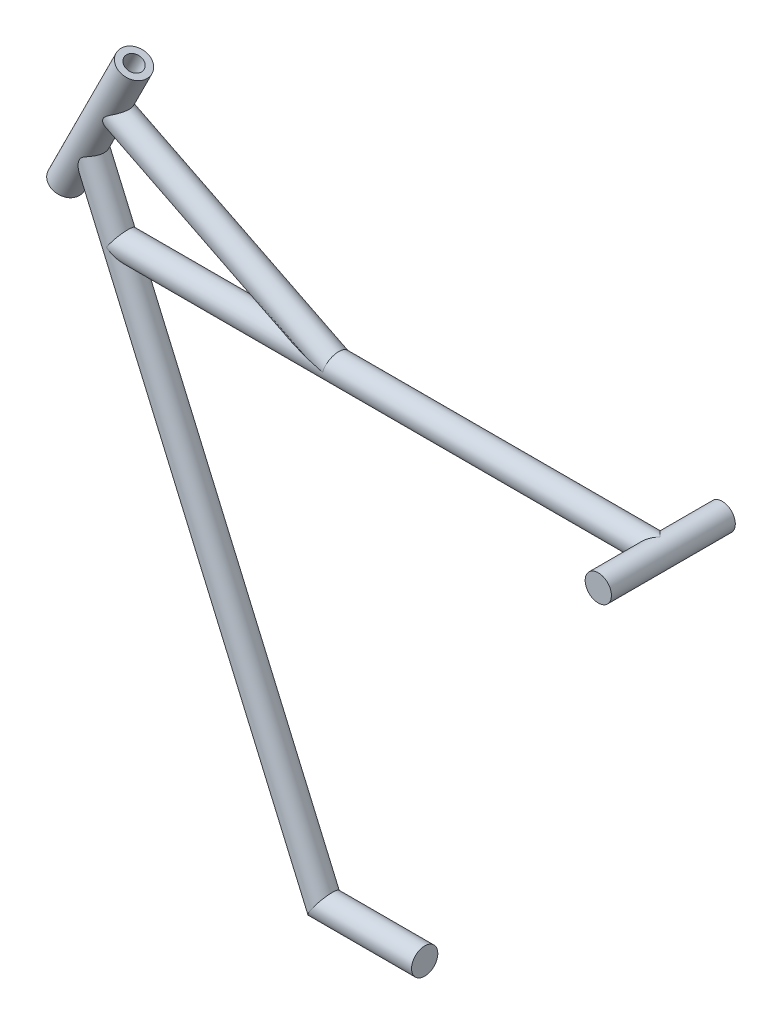
SolidWorks part; units mm, degrees
ref_plane "Спереди" through (0, 0, 0) normal (0, 0, 1) x (1, 0, 0)
ref_plane "Сверху" through (0, 0, 0) normal (0, 1, 0) x (1, 0, 0)
ref_plane "Справа" through (0, 0, 0) normal (1, 0, 0) x (0, 0, -1)
sketch "Эскиз1" plane through (65.3567, 130.5673, 0) normal (0.4476, 0.8942, 0) x (0.8942, -0.4476, 0)
  circle A0 centre (-752.4657, 0) radius 15
  circle A1 centre (-752.4657, 0) radius 8.538
extrude "Бобышка-Вытянуть1" add sketch "Эскиз1" along normal blind 155
sketch "шлях" plane through (0, 0, 0) normal (0, 0, 1) x (1, 0, 0)
  line L1 (-344.3559, -42.0343) -> (-584.115, 511.7691)
  line L5 (-344.3559, -42.0343) -> (-240.4718, -42.0343)
  dimension "D1" = 246.591
ref_plane "Плоскость4" through (-240.4718, 0, 0) normal (1, 0, 0) x (0, 0, -1)
sketch "профіль" plane through (-240.4718, 0, 0) normal (1, 0, 0) x (0, 0, -1)
  circle A0 centre (0, -41.4928) radius 13.45
sweep "По траектории1" add profiles "профіль" path "шлях"
ref_plane "Плоскость5" through (0, -42.0343, 0) normal (0, 1, 0) x (1, 0, 0)
ref_plane "Плоскость7" through (0, 0, 50) normal (0, 0, 1) x (1, 0, 0)
sketch "Эскиз5" plane through (0, 0, 50) normal (0, 0, 1) x (1, 0, 0)
  line L0 (43.8257, 180.5593) -> (-9.8854, 49.4555) construction
  line L1 (100.1108, 212.4383) -> (0.7865, 441.8608)
  line L3 (-4.1424, -42.0343) -> (100.1108, 212.4383)
  line L4 (-335.1669, -28.0428) -> (-568.7095, 511.4016) construction
  line L5 (-4.1424, -42.0343) -> (-279.1424, -42.0343)
  dimension "D1" = 250
  dimension "D2" = 39.9983
  dimension "D3" = 275
  dimension "D4" = 275
ref_plane "Плоскость8" through (0.7865, 441.8608, 50) normal (-0.3973, 0.9177, 0) x (0.9177, 0.3973, 0)
sketch "Эскиз10" plane through (0, 0, 0) normal (0, 0, 1) x (1, 0, 0)
  circle A0 centre (0.7865, 441.8608) radius 13.45
extrude "Бобышка-Вытянуть2" add sketch "Эскиз10" along normal mid plane 126.9 contours A0
sketch "Эскиз11" plane through (0, 0, 0) normal (0, 0, 1) x (1, 0, 0)
  line L0 (0.7865, 441.8608) -> (-553.4001, 441.8608)
  point P5 (-553.4001, 441.8608)
ref_plane "Плоскость10" through (0.7865, 441.8608, 0) normal (-1, 0, 0) x (0, 0, 1)
sketch "Эскиз12" plane through (0.7865, 441.8608, 0) normal (-1, 0, 0) x (0, 0, 1)
  circle A0 centre (0, 0) radius 13.45
  dimension "D1" = 26.9
sweep "По траектории7" add profiles "Эскиз12" path "Эскиз11"
sketch "Эскиз13" plane through (0, 0, 0) normal (0, 0, 1) x (1, 0, 0)
  line L0 (-562.1123, 557.2874) -> (-331.5169, 441.8608)
  line L1 (-498.7232, 455.3108) -> (-498.7232, 428.4108) construction
  line L2 (0.7865, 455.3108) -> (-553.4001, 455.3108) construction
  line L3 (-553.4001, 428.4108) -> (0.7865, 428.4108) construction
  line L4 (-498.7232, 441.8608) -> (-164.3106, 441.8608) construction
  line L5 (-538.1384, 605.9864) -> (-607.5185, 467.3812) construction
  line L6 (-530.5035, 602.1647) -> (-545.7732, 609.8081) construction
  line L7 (-620.9319, 474.0954) -> (-594.1051, 460.667) construction
ref_plane "Плоскость11" through (-331.5169, 441.8608, 0) normal (0.8942, -0.4476, 0) x (0, 0, -1)
sketch "Эскиз14" plane through (-331.5169, 441.8608, 0) normal (0.8942, -0.4476, 0) x (0, 0, -1)
  circle A0 centre (0, 0) radius 13.45
sweep "По траектории8" add profiles "Эскиз14" path "Эскиз13"
